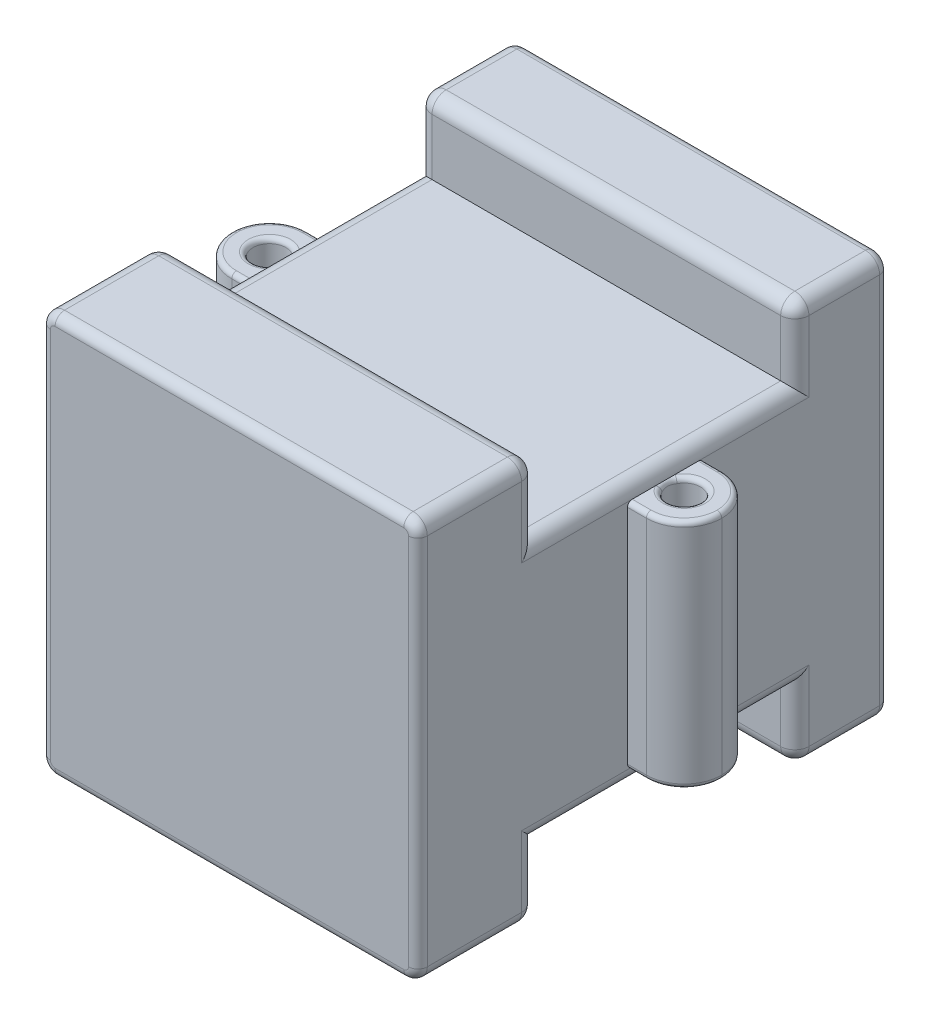
SolidWorks part; units mm, degrees
ref_plane "Plan de face" through (0, 0, 0) normal (0, 0, 1) x (1, 0, 0)
ref_plane "Plan de dessus" through (0, 0, 0) normal (0, 1, 0) x (1, 0, 0)
ref_plane "Plan de droite" through (0, 0, 0) normal (1, 0, 0) x (0, 0, -1)
sketch "Esquisse1" plane through (0, 0, 0) normal (0, 0, 1) x (1, 0, 0)
  line L1 (-40, 42.6) -> (40, 42.6)
  line L2 (-40, 42.6) -> (-40, -42.6)
  line L3 (-40, -42.6) -> (40, -42.6)
  line L4 (40, 42.6) -> (40, -42.6)
  line L5 (-40, 42.6) -> (40, -42.6) construction
  line L6 (-40, -42.6) -> (40, 42.6) construction
  point P0 (0, 0)
  dimension "D1" = 85.2
  dimension "D2" = 80
extrude "Boss.-Extru.1" add sketch "Esquisse1" along normal blind 100
sketch "Esquisse2" plane through (-40, 0, 0) normal (-1, 0, 0) x (0, 0, 1)
  line L0 (0, 0) -> (100, 0) construction
  line L1 (100, 42.6) -> (100, -42.6) construction
  line L2 (50, 0) -> (50, 42.6) construction
  line L3 (100, 42.6) -> (0, 42.6) construction
  line L4 (50, 42.6) -> (50, -42.6) construction
  line L5 (100, -42.6) -> (0, -42.6) construction
  line L6 (0, 42.6) -> (0, -42.6) construction
  line L7 (75, 42.6) -> (20, 42.6)
  line L8 (75, 42.6) -> (75, 27.6)
  line L9 (75, 27.6) -> (20, 27.6)
  line L10 (20, 42.6) -> (20, 27.6)
  line L12 (20, -42.6) -> (75, -42.6)
  line L13 (20, -42.6) -> (20, -27.6)
  line L14 (20, -27.6) -> (75, -27.6)
  line L15 (75, -42.6) -> (75, -27.6)
  dimension "D1" = 25
  dimension "D2" = 20
  dimension "D3" = 15
  dimension "D4" = 20
  dimension "D5" = 25
  dimension "D6" = 15
  dimension "D7" = 55
extrude "Enlèv. mat.-Extru.1" cut sketch "Esquisse2" against normal blind 100
fillet "Congé1" radius 3 4 edges at (0, -42.6, 75) (0, -42.6, 20) (0, 42.6, 75) (0, 42.6, 20)
fillet "Congé2" radius 2 4 edges at (40, 0, 0) (0, -42.6, 0) (-40, 0, 0) (0, 42.6, 0)
fillet "Congé3" radius 2 4 edges at (0, -42.6, 100) (-40, 0, 100) (0, 42.6, 100) (40, 0, 100)
fillet "Congé4" radius 3 36 edges at (-39.4142, -42.0142, 99.4142) (-39.4142, 42.0142, 99.4142) (39.4142, 42.0142, 99.4142) (39.4142, -42.0142, 99.4142) (-39.4142, -42.0142, 0.5858) (-39.4142, 42.0142, 0.5858) (39.4142, 42.0142, 0.5858) (39.4142, -42.0142, 0.5858) (40, -42.6, 9.5) (40, -41.7213, 19.1213) (40, 42.6, 9.5) (40, 41.7213, 19.1213) (-40, 42.6, 9.5) (-40, 41.7213, 19.1213) (-40, -42.6, 9.5) (-40, -41.7213, 19.1213) (40, -42.6, 88) (40, -41.7213, 75.8787) (40, 42.6, 88) (40, 41.7213, 75.8787) (-40, 42.6, 88) (-40, 41.7213, 75.8787) (-40, -42.6, 88) (-40, -41.7213, 75.8787) (40, -33.6, 20) (40, 33.6, 20) (40, 27.6, 47.5) (-40, 33.6, 20) (-40, -33.6, 20) (40, -27.6, 47.5) (40, -33.6, 75) (40, 33.6, 75) (-40, 33.6, 75) (-40, -33.6, 75) (-40, -27.6, 47.5) (-40, 27.6, 47.5)
sketch "Esquisse3" plane through (0, 0, 0) normal (0, 0, -1) x (-1, 0, 0)
  circle A0 centre (0, 0) radius 25.5
  dimension "D1" = 51
extrude "Enlèv. mat.-Extru.3" cut sketch "Esquisse3" against normal blind 100
sketch "Esquisse5" plane through (40, 0, 0) normal (1, 0, 0) x (0, 0, -1)
  line L1 (-78, 24.6) -> (-17, 24.6)
  line L2 (-78, 24.6) -> (-78, -24.6)
  line L3 (-78, -24.6) -> (-17, -24.6)
  line L4 (-17, 24.6) -> (-17, -24.6)
extrude "Boss.-Extru.2" add sketch "Esquisse5" along normal blind 20
sketch "Esquisse7" plane through (0, -24.6, 0) normal (0, -1, 0) x (1, 0, 0)
  line L0 (60, 78) -> (60, 17) construction
  line L1 (40, 78) -> (60, 78)
  line L2 (40, 78) -> (40, 68)
  line L3 (40, 68) -> (60, 68)
  line L4 (60, 78) -> (60, 68)
  line L5 (40, 78) -> (40, 17) construction
  line L6 (60, 17) -> (40, 17)
  line L7 (60, 17) -> (60, 27)
  line L8 (60, 27) -> (40, 27)
  line L9 (40, 17) -> (40, 27)
  dimension "D1" = 10
  dimension "D2" = 10
extrude "Enlèv. mat.-Extru.4" cut sketch "Esquisse7" against normal blind 60
sketch "Esquisse8" plane through (0, -24.6, 0) normal (0, -1, 0) x (1, 0, 0)
  line L0 (60, 27) -> (40, 27) construction
  line L1 (60, 68) -> (55, 68)
  line L2 (60, 68) -> (60, 27)
  line L3 (60, 27) -> (55, 27)
  line L4 (55, 68) -> (55, 27)
  dimension "D1" = 5
extrude "Enlèv. mat.-Extru.5" cut sketch "Esquisse8" against normal blind 78
fillet "Congé6" radius 20 2 edges at (55, 0, 27) (55, 0, 68)
sketch "Esquisse9" plane through (0, -24.6, 0) normal (0, -1, 0) x (1, 0, 0)
  line L0 (55, 47.5) -> (40, 47.5) construction
  line L1 (55, 48.6351) -> (55, 46.3649) construction
  line L2 (40, 68) -> (40, 27) construction
  line L3 (40, 68) -> (40, 55.5)
  line L4 (40, 55.5) -> (52, 55.5)
  line L5 (52, 55.5) -> (52, 39.5)
  line L6 (52, 39.5) -> (40, 39.5)
  line L7 (40, 39.5) -> (40, 27)
  line L8 (40, 27) -> (62.5234, 29.0461)
  line L9 (62.5234, 29.0461) -> (57.9649, 79.2245)
  line L10 (57.9649, 79.2245) -> (40, 68)
  circle A0 centre (44, 47.5) radius 3.5
  dimension "D1" = 7
  dimension "D2" = 4
  dimension "D4" = 8
  dimension "D3" = 8
  dimension "D5" = 8
extrude "Enlèv. mat.-Extru.7" cut sketch "Esquisse9" against normal blind 78
fillet "Congé7" radius 8 2 edges at (52, 0, 55.5) (52, 0, 39.5)
sketch "Esquisse10" plane through (-40, 0, 0) normal (-1, 0, 0) x (0, 0, 1)
  line L1 (17, 24.6) -> (78, 24.6)
  line L2 (17, 24.6) -> (17, -24.6)
  line L3 (17, -24.6) -> (78, -24.6)
  line L4 (78, 24.6) -> (78, -24.6)
extrude "Boss.-Extru.4" add sketch "Esquisse10" along normal blind 15
sketch "Esquisse13" plane through (0, 24.6, 0) normal (0, 1, 0) x (1, 0, 0)
  line L0 (-40, -78) -> (-40, -17) construction
  line L1 (-40, -39.5) -> (-52, -39.5)
  line L2 (-40, -39.5) -> (-40, -55.5)
  line L3 (-40, -55.5) -> (-52, -55.5)
  line L4 (-52, -39.5) -> (-52, -55.5)
  line L6 (-55, -78) -> (-40, -78) construction
  line L7 (-55, -17) -> (-40, -17) construction
  line L8 (-40, -55.5) -> (-40, -78)
  line L9 (-40, -78) -> (-110.7986, -93.3805)
  line L10 (-110.7986, -93.3805) -> (-110.7986, -4.487)
  line L11 (-110.7986, -4.487) -> (-52, -4.487)
  line L12 (-52, -4.487) -> (-40, -17)
  line L13 (-40, -17) -> (-40, -39.5)
  line L14 (-52, -39.5) -> (-52, -55.5)
  line L15 (-40, -55.5) -> (-40, -78)
  line L16 (-40, -39.5) -> (-52, -39.5)
  line M5 (-40, -78) -> (-40, -17)
  line M6 (-40, -17) -> (-55, -17)
  line M7 (-55, -17) -> (-55, -78)
  line M8 (-55, -78) -> (-40, -78)
  dimension "D1" = 16
  dimension "D2" = 12
  dimension "D3" = 22.5
  dimension "D4" = 22.5
extrude "Enlèv. mat.-Extru.9" cut sketch "Esquisse13" against normal blind 114 contours L12 L11 L10 L9 M8 M7 M6 | L4 L1 L3 M5 M6 M7 M8 region at (-46, 24.6, 38.8718) region at (-82.6088, 24.6, 45.3464)
fillet "Congé8" radius 8 2 edges at (-52, 0, 39.5) (-52, 0, 55.5)
sketch "Esquisse14" plane through (0, -24.6, 0) normal (0, -1, 0) x (1, 0, 0)
  line L0 (-52, 47.5) -> (-40, 47.5) construction
  line L1 (-40, 39.5) -> (-40, 55.5) construction
  circle A0 centre (-44, 47.5) radius 3.5
  dimension "D1" = 7
  dimension "D2" = 4
extrude "Enlèv. mat.-Extru.10" cut sketch "Esquisse14" against normal blind 114
fillet "Congé9" radius 1 20 edges at (47.5, 24.6, 47.5) (42, 24.6, 39.5) (49.6569, 24.6, 41.8431) (49.6569, 24.6, 53.1569) (42, 24.6, 55.5) (-42, 24.6, 55.5) (-42, 24.6, 39.5) (-49.6569, 24.6, 41.8431) (-49.6569, 24.6, 53.1569) (-40.5, 24.6, 47.5) (-40.5, -24.6, 47.5) (-42, -24.6, 55.5) (-49.6569, -24.6, 53.1569) (-49.6569, -24.6, 41.8431) (-42, -24.6, 39.5) (42, -24.6, 39.5) (49.6569, -24.6, 41.8431) (42, -24.6, 55.5) (49.6569, -24.6, 53.1569) (47.5, -24.6, 47.5)
fillet "Congé10" radius 1 2 edges at (-25.5, 0, 0) (-25.5, 0, 100)
sketch "Esquisse16" plane through (0, 0, 0) normal (0, 1, 0) x (1, 0, 0)
  line L0 (-37, -78) -> (-37, -98) construction
  line L1 (-37, -92.4094) -> (37, -92.4094)
  line L2 (-37, -92.4094) -> (-37, -100)
  line L3 (-37, -100) -> (37, -100)
  line L4 (37, -92.4094) -> (37, -100)
  line L5 (37, -100) -> (37, -98) construction
  line L6 (37, -100) -> (-37, -100) construction
extrude "Boss.-Extru.5" add sketch "Esquisse16" against normal blind 30 and the other way blind 30
